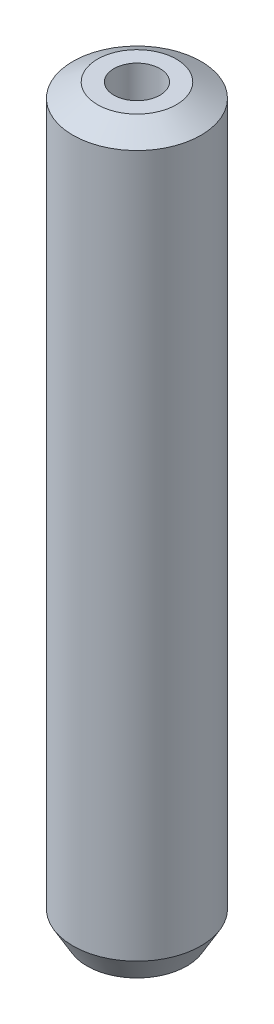
SolidWorks part; units mm, degrees
ref_plane "Front Plane" through (0, 0, 0) normal (0, 0, 1) x (1, 0, 0)
ref_plane "Top Plane" through (0, 0, 0) normal (0, 1, 0) x (1, 0, 0)
ref_plane "Right Plane" through (0, 0, 0) normal (1, 0, 0) x (0, 0, -1)
sketch "Sketch1" plane through (0, 0, 0) normal (0, 1, 0) x (1, 0, 0)
  circle A0 centre (0, 0) radius 7.5
  dimension "SHAFT_OD" = 15
extrude "Boss-Extrude1" add sketch "Sketch1" along normal blind 86.7572
sketch "Sketch2" plane through (0, 0, 0) normal (0, 1, 0) x (1, 0, 0)
  circle A0 centre (0, 0) radius 2.7
  dimension "BORE_D" = 5.4
extrude "Cut-Extrude1" cut sketch "Sketch2" along normal through all
chamfer "Chamfer1" distance 1.6615 angle 60 2 edges at (0, 86.7572, 7.5) (0, 0, 7.5) first distance on face at (0, 86.7572, 7.5) first distance on face at (0, 0, 2.7)
